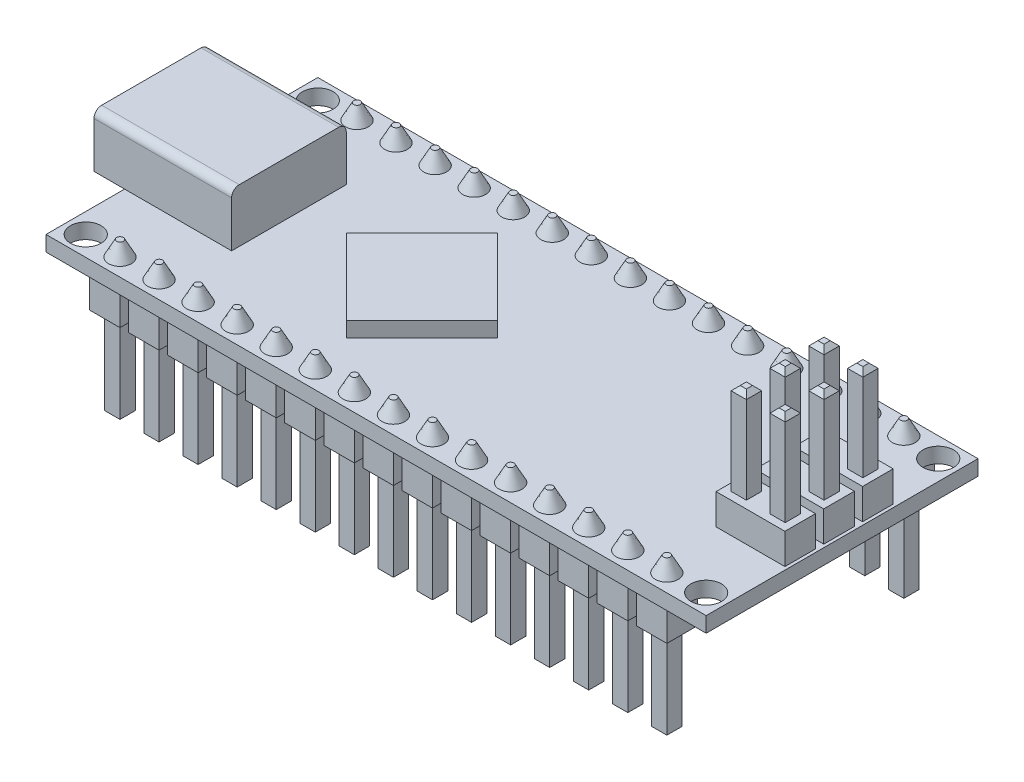
SolidWorks part; units mm, degrees
ref_plane "Plano frontal" through (0, 0, 0) normal (0, 0, 1) x (1, 0, 0)
ref_plane "Plano superior" through (0, 0, 0) normal (0, 1, 0) x (1, 0, 0)
ref_plane "Plano direito" through (0, 0, 0) normal (1, 0, 0) x (0, 0, -1)
sketch "Esboço1" plane through (0, 0, 0) normal (0, 1, 0) x (1, 0, 0)
  line L1 (-21.59, -8.89) -> (21.59, -8.89)
  line L2 (-21.59, -8.89) -> (-21.59, 8.89)
  line L3 (-21.59, 8.89) -> (21.59, 8.89)
  line L4 (21.59, -8.89) -> (21.59, 8.89)
  line L5 (-21.59, -8.89) -> (21.59, 8.89) construction
  line L6 (-21.59, 8.89) -> (21.59, -8.89) construction
  point P0 (0, 0)
  dimension "D1" = 43.18
  dimension "D2" = 17.78
extrude "Ressalto-extrusão1" add sketch "Esboço1" along normal blind 1
sketch "Esboço2" plane through (0, 0, 0) normal (0, -1, 0) x (1, 0, 0)
  line L0 (-21.59, -8.89) -> (-21.59, 8.89) construction
  line L1 (-18.89, 8.75) -> (-16.89, 8.75)
  line L2 (-18.89, 8.75) -> (-18.89, 6.75)
  line L3 (-18.89, 6.75) -> (-16.89, 6.75)
  line L4 (-16.89, 8.75) -> (-16.89, 6.75)
  line L5 (-18.89, 8.75) -> (-16.89, 6.75) construction
  line L6 (-18.89, 6.75) -> (-16.89, 8.75) construction
  line L7 (-18.89, -6.75) -> (-16.89, -6.75)
  line L8 (-18.89, -6.75) -> (-18.89, -8.75)
  line L9 (-18.89, -8.75) -> (-16.89, -8.75)
  line L10 (-16.89, -6.75) -> (-16.89, -8.75)
  line L11 (-18.89, -6.75) -> (-16.89, -8.75) construction
  line L12 (-18.89, -8.75) -> (-16.89, -6.75) construction
  line L13 (-16.89, -8.75) -> (-16.89, -8.89) construction
  line L14 (21.59, -8.89) -> (-21.59, -8.89) construction
  line L15 (-16.89, 8.75) -> (-16.89, 8.89) construction
  line L16 (-21.59, 8.89) -> (21.59, 8.89) construction
  point P0 (-17.89, 7.75)
  point P5 (-17.89, -7.75)
  dimension "D1" = 2
  dimension "D2" = 13.5
  dimension "D3" = 2.7
extrude "Ressalto-extrusão2" add sketch "Esboço2" along normal blind 2
sketch "Esboço3" plane through (0, -2, 0) normal (0, -1, 0) x (1, 0, 0)
  line L1 (-18.39, 8.25) -> (-17.39, 8.25)
  line L2 (-18.39, 8.25) -> (-18.39, 7.25)
  line L3 (-18.39, 7.25) -> (-17.39, 7.25)
  line L4 (-17.39, 8.25) -> (-17.39, 7.25)
  line L5 (-18.39, 8.25) -> (-17.39, 7.25) construction
  line L6 (-18.39, 7.25) -> (-17.39, 8.25) construction
  line L7 (-18.39, -8.25) -> (-17.39, -8.25)
  line L8 (-18.39, -8.25) -> (-18.39, -7.25)
  line L9 (-18.39, -7.25) -> (-17.39, -7.25)
  line L10 (-17.39, -8.25) -> (-17.39, -7.25)
  line L11 (-18.39, -8.25) -> (-17.39, -7.25) construction
  line L12 (-18.39, -7.25) -> (-17.39, -8.25) construction
  point P0 (-17.89, 7.75)
  point P6 (-17.89, -7.75)
  dimension "D1" = 1
extrude "Ressalto-extrusão3" add sketch "Esboço3" along normal blind 6
sketch "Esboço5" plane through (0, 1, 0) normal (0, 1, 0) x (1, 0, 0)
  line L0 (-18.89, 8.75) -> (-16.89, 6.75) construction
  circle A0 centre (-17.89, 7.75) radius 0.75
  circle A1 centre (-17.89, -7.75) radius 0.75
  dimension "D1" = 1.5
extrude "Ressalto-extrusão5" add sketch "Esboço5" along normal blind 1 draft 28
chamfer "Chanfro1" distance 0.3 angle 45 8 edges at (-17.39, -8, 7.75) (-17.89, -8, 8.25) (-18.39, -8, 7.75) (-17.89, -8, 7.25) (-17.89, -8, -8.25) (-18.39, -8, -7.75) (-17.89, -8, -7.25) (-17.39, -8, -7.75)
pattern_linear "Padrão linear1" count 15 spacing 2.555 along (1, 0, 0) of "Ressalto-extrusão2", "Ressalto-extrusão3", "Chanfro1", "Ressalto-extrusão5"
sketch "Esboço4" plane through (0, 1, 0) normal (0, 1, 0) x (1, 0, 0)
  line L0 (-10.8397, 0) -> (-5.89, 4.9497)
  line L1 (-5.89, 4.9497) -> (-0.9403, 0)
  line L2 (-0.9403, 0) -> (-5.89, -4.9497)
  line L3 (-5.89, -4.9497) -> (-10.8397, 0)
  line L4 (-5.89, 4.9497) -> (-5.89, 8.89) construction
  line L5 (21.59, 8.89) -> (-21.59, 8.89) construction
  line L6 (-5.89, -4.9497) -> (-5.89, -8.89) construction
  line L7 (-21.59, -8.89) -> (21.59, -8.89) construction
  line L8 (-21.59, 8.89) -> (-21.59, -8.89) construction
  dimension "D1" = 7
  dimension "D2" = 15.7
extrude "Ressalto-extrusão4" add sketch "Esboço4" along normal blind 1
sketch "Esboço6" plane through (0, 1, 0) normal (0, 1, 0) x (1, 0, 0)
  line L0 (-23.59, 0) -> (-21.59, 0) construction
  line L1 (-14.59, 3.75) -> (-23.59, 3.75)
  line L2 (-14.59, 3.75) -> (-14.59, -3.75)
  line L3 (-14.59, -3.75) -> (-23.59, -3.75)
  line L4 (-23.59, 3.75) -> (-23.59, -3.75)
  line L5 (-21.59, 8.89) -> (-21.59, -8.89) construction
  dimension "D1" = 7.5
  dimension "D2" = 9
  dimension "D3" = 2
extrude "Ressalto-extrusão6" add sketch "Esboço6" along normal blind 3.5
sketch "Esboço7" plane through (0, 1, 0) normal (0, 1, 0) x (1, 0, 0)
  line L0 (-20.29, 7.59) -> (20.29, 7.59) construction
  line L1 (20.29, 7.59) -> (20.29, -7.59) construction
  line L2 (20.29, -7.59) -> (-20.29, -7.59) construction
  line L3 (-20.29, -7.59) -> (-20.29, 7.59) construction
  line L4 (-20.29, 7.59) -> (20.29, -7.59) construction
  line L5 (21.59, 8.89) -> (-21.59, 8.89) construction
  line L6 (-21.59, 8.89) -> (-21.59, 3.75) construction
  circle A0 centre (-20.29, 7.59) radius 1
  circle A1 centre (-20.29, -7.59) radius 1
  circle A2 centre (20.29, -7.59) radius 1
  circle A3 centre (20.29, 7.59) radius 1
  dimension "D1" = 2
  dimension "D2" = 1.3
  dimension "D3" = 1.3
extrude "Corte-extrusão1" cut sketch "Esboço7" against normal through all
sketch "Esboço8" plane through (-23.59, 0, 0) normal (-1, 0, 0) x (0, 0, 1)
  line L0 (-3.75, 4.5) -> (3.75, 1) construction
  line L1 (-3.75, 4.5) -> (3.75, 4.5) construction
  line L2 (-3.25, 1.5) -> (3.25, 1.5)
  line L3 (-3.25, 1.5) -> (-3.25, 4)
  line L4 (-3.25, 4) -> (3.25, 4)
  line L5 (3.25, 1.5) -> (3.25, 4)
  line L6 (-3.25, 1.5) -> (3.25, 4) construction
  line L7 (-3.25, 4) -> (3.25, 1.5) construction
  line L8 (3.75, 4.5) -> (3.75, 1) construction
  line L10 (2.5, 2.25) -> (-2.5, 2.25)
  line L11 (2.5, 2.25) -> (2.5, 3.25)
  line L12 (2.5, 3.25) -> (-2.5, 3.25)
  line L13 (-2.5, 2.25) -> (-2.5, 3.25)
  line L14 (2.5, 2.25) -> (-2.5, 3.25) construction
  line L15 (2.5, 3.25) -> (-2.5, 2.25) construction
  point P4 (0, 2.75)
  point P13 (0, 2.75)
  dimension "D1" = 0.5
  dimension "D2" = 0.5
  dimension "D3" = 5
  dimension "D4" = 1
extrude "Corte-extrusão2" cut sketch "Esboço8" against normal blind 7
sketch "Esboço10" plane through (0, 1, 0) normal (0, 1, 0) x (1, 0, 0)
  line L0 (21.39, 0) -> (21.59, 0) construction
  line L1 (16.89, 1) -> (21.39, 1)
  line L2 (16.89, 1) -> (16.89, -1)
  line L3 (16.89, -1) -> (21.39, -1)
  line L4 (21.39, 1) -> (21.39, -1)
  line L5 (21.59, -8.89) -> (21.59, 8.89) construction
  dimension "D1" = 2
  dimension "D2" = 0.2
  dimension "D3" = 4.5
extrude "Ressalto-extrusão7" add sketch "Esboço10" along normal blind 2
sketch "Esboço11" plane through (0, 3, 0) normal (0, 1, 0) x (1, 0, 0)
  line L0 (17.37, 0.5) -> (18.37, -0.5) construction
  line L1 (17.37, 0.5) -> (18.37, 0.5)
  line L2 (17.37, 0.5) -> (17.37, -0.5)
  line L3 (17.37, -0.5) -> (18.37, -0.5)
  line L4 (18.37, 0.5) -> (18.37, -0.5)
  line L5 (19.91, 0.5) -> (20.91, 0.5)
  line L6 (19.91, 0.5) -> (19.91, -0.5)
  line L7 (19.91, -0.5) -> (20.91, -0.5)
  line L8 (20.91, 0.5) -> (20.91, -0.5)
  line L9 (20.91, -0.5) -> (19.91, 0.5) construction
  line L10 (17.87, 0) -> (20.41, 0) construction
  line L11 (19.14, -1) -> (19.14, 1) construction
  line L12 (16.89, -1) -> (21.39, -1) construction
  line L13 (21.39, 1) -> (16.89, 1) construction
  point P16 (19.14, 0)
  dimension "D1" = 2.54
  dimension "D2" = 1
extrude "Ressalto-extrusão8" add sketch "Esboço11" along normal blind 6
chamfer "Chanfro2" distance 0.3 angle 45 8 edges at (17.87, 9, -0.5) (18.37, 9, 0) (17.87, 9, 0.5) (17.37, 9, 0) (20.41, 9, -0.5) (20.91, 9, 0) (20.41, 9, 0.5) (19.91, 9, 0)
pattern_linear "Padrão linear2" count 2 spacing 2.54 along (0, 0, 1) count 2 spacing 2.54 along (0, 0, -1) of "Chanfro2", "Ressalto-extrusão8", "Ressalto-extrusão7"
fillet "Filete1" radius 0.5 2 edges at (-19.09, 4.5, -3.75) (-19.09, 4.5, 3.75)
